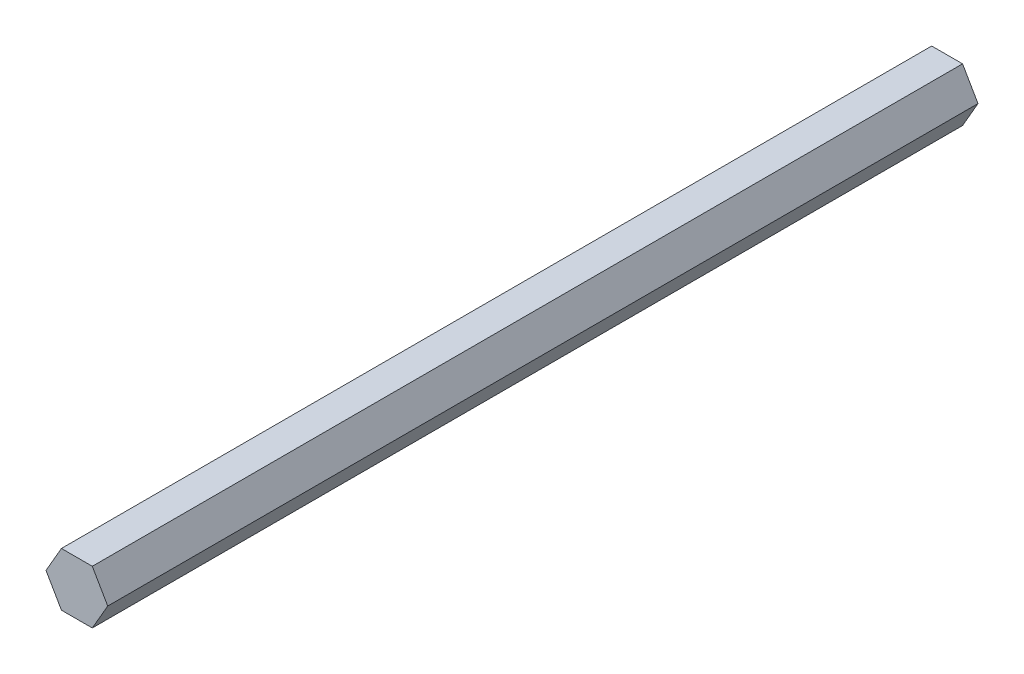
SolidWorks part; units mm, degrees
ref_plane "Front Plane" through (0, 0, 0) normal (0, 0, 1) x (1, 0, 0)
ref_plane "Top Plane" through (0, 0, 0) normal (0, 1, 0) x (1, 0, 0)
ref_plane "Right Plane" through (0, 0, 0) normal (1, 0, 0) x (0, 0, -1)
sketch "Sketch1" plane through (0, 0, 0) normal (0, 0, 1) x (1, 0, 0)
  line L1 (3.6662, 6.35) -> (-3.6662, 6.35)
  line L2 (-3.6662, 6.35) -> (-7.3323, 0)
  line L3 (-7.3323, 0) -> (-3.6662, -6.35)
  line L4 (-3.6662, -6.35) -> (3.6662, -6.35)
  line L5 (3.6662, -6.35) -> (7.3323, 0)
  line L6 (7.3323, 0) -> (3.6662, 6.35)
  circle A0 centre (0, 0) radius 6.35 construction
  dimension "D1" = 12.7
extrude "Boss-Extrude1" add sketch "Sketch1" along normal mid plane 206.756
ref_axis "Axis1" through (0, 0, -83.82) along (0, 0, 1)
